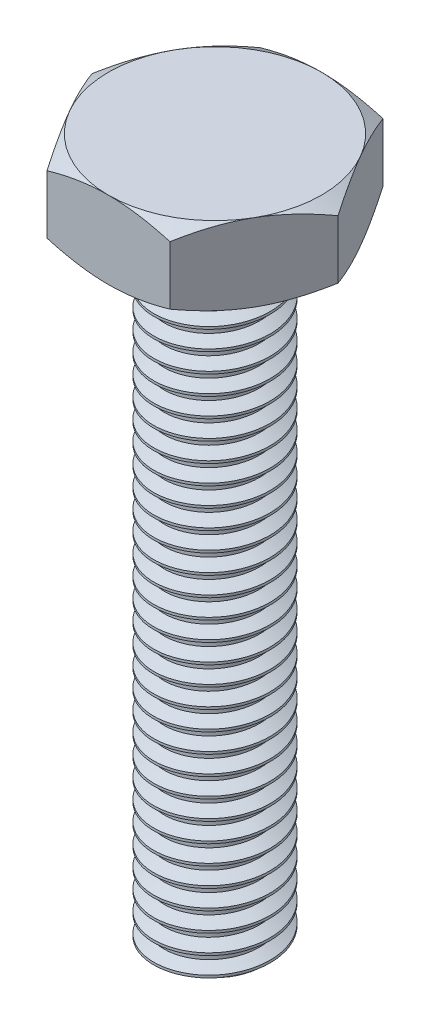
SolidWorks part; units mm, degrees
ref_plane "Piano frontale" through (0, 0, 0) normal (0, 0, 1) x (1, 0, 0)
ref_plane "Piano superiore" through (0, 0, 0) normal (0, 1, 0) x (1, 0, 0)
ref_plane "Piano destro" through (0, 0, 0) normal (1, 0, 0) x (0, 0, -1)
sketch "Schizzo1" plane through (0, 0, 0) normal (0, 1, 0) x (1, 0, 0)
  line L1 (1.5877, 2.75) -> (-1.5877, 2.75)
  line L2 (-1.5877, 2.75) -> (-3.1754, 0)
  line L3 (-3.1754, 0) -> (-1.5877, -2.75)
  line L4 (-1.5877, -2.75) -> (1.5877, -2.75)
  line L5 (1.5877, -2.75) -> (3.1754, 0)
  line L6 (3.1754, 0) -> (1.5877, 2.75)
  circle A0 centre (0, 0) radius 2.75 construction
  dimension "D1" = 5.5
extrude "Estrusione-Estrusione1" add sketch "Schizzo1" against normal blind 2 contours L1 L2 L3 L4 L5 L6
sketch "Schizzo3" plane through (0, 0, 0) normal (1, 0, 0) x (0, 0, -1)
  line L0 (0, 0) -> (0, 50000) construction
  line L1 (0.4056, 1.3536) -> (4.111, -0.7858)
  line L2 (4.111, -0.7858) -> (4.7852, 1.09)
  line L3 (4.7852, 1.09) -> (0.4056, 1.3536)
  point P5 (2.75, 0)
  dimension "D1" = 60
revolve "Taglia-Rivoluzione4" cut sketch "Schizzo3" angle 360 about L0
ref_plane "Piano1" through (0, -1, 0) normal (0, 1, 0) x (1, 0, 0)
mirror "Specchia1" about plane through (0, -1, 0) normal (0, 1, 0) of "Taglia-Rivoluzione4"
sketch "Schizzo4" plane through (0, -2, 0) normal (0, -1, 0) x (1, 0, 0)
  circle A0 centre (0, 0) radius 1.5
  arc A1 (-2.3816, 1.375) -> (-2.3816, -1.375) centre (0, 0) ccw construction
  dimension "D1" = 3
extrude "Estrusione-Estrusione2" add sketch "Schizzo4" along normal blind 16
thread "Filettatura1" pitch 0.5 method cut profile "Profilo filettatura1" start angle 1, offset 0, length 0, pitch 0.5, diameter 3
ref_plane "Piano2" through (-1.4998, -2, -0.0262) normal (-0.0175, 0, 0.9998) x (-0.9998, 0, -0.0175)
sketch "Profilo filettatura1" plane through (-1.4998, -2, -0.0262) normal (-0.0175, 0, 0.9998) x (-0.9998, 0, -0.0175)
  line L0 (0, 0) -> (0, 0.5) construction
  line L11 (0, 0) -> (0, 0.4375)
  line L12 (0, 0.4375) -> (-0.2706, 0.2812)
  line L13 (-0.2706, 0.2812) -> (-0.2706, 0.1562)
  line L15 (-0.2706, 0.1562) -> (0, 0)
  line L17 (-0.2706, 0.2187) -> (0, 0.2187) construction
  point P2 (0, 0)
  dimension "Pitch" = 0.5
  dimension "Profile_Angle" = 60
  dimension "Profile_Land" = 0.125
  dimension "Profile_Height" = 0.2706
